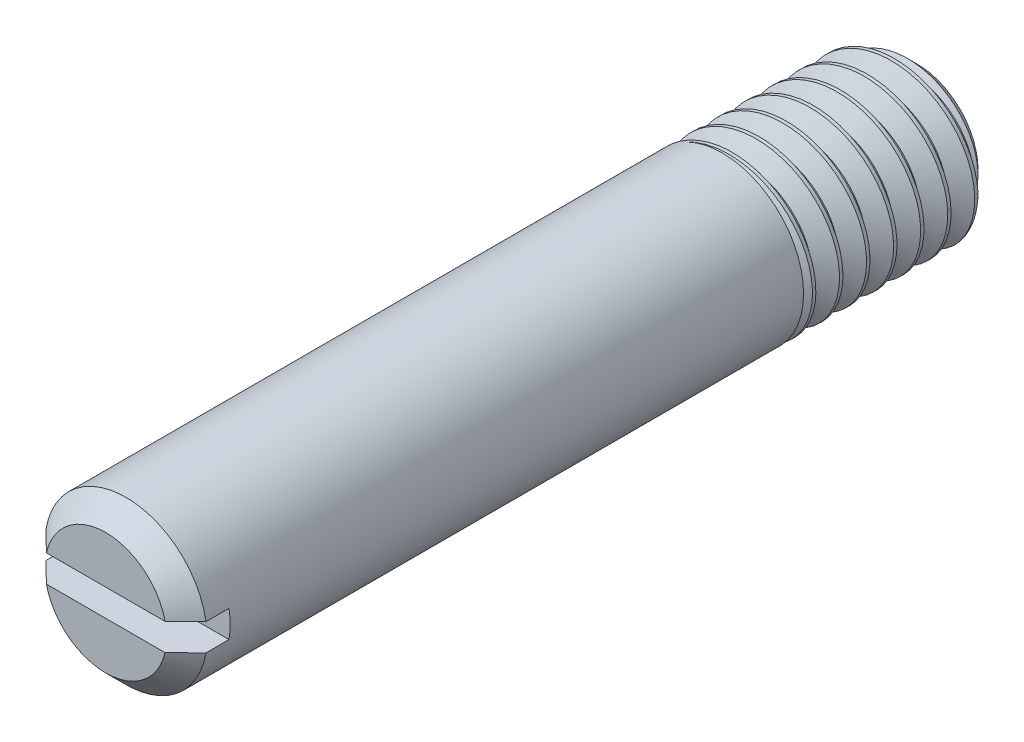
SolidWorks part; units mm, degrees
ref_plane "Front Plane" through (0, 0, 0) normal (0, 0, 1) x (1, 0, 0)
ref_plane "Top Plane" through (0, 0, 0) normal (0, 1, 0) x (1, 0, 0)
ref_plane "Right Plane" through (0, 0, 0) normal (1, 0, 0) x (0, 0, -1)
sketch "Sketch1" plane through (0, 0, 0) normal (1, 0, 0) x (0, 0, -1)
  line L0 (-22.8, 0) -> (7.2, 0) construction
  line L1 (7.2, 3) -> (7.2, -3) construction
  line L2 (-22.8, 0.5) -> (-22.8, -0.5) construction
  line L3 (-22.8, -0.5) -> (-21.2, -0.5) construction
  line L4 (7.2, 3) -> (6.2, 3) construction
  line L5 (6.2, 3) -> (0, 3) construction
  line L6 (0, 3) -> (-22.8, 3) construction
  point P5 (7.2, 0)
  point P9 (0, 0)
  dimension "Oall Length" = 30
  dimension "Thread Diameter" = 6
  dimension "Thread Length" = 7.2
  dimension "Slot Width n" = 1
  dimension "Slot Depth t" = 1.6
  dimension "Pitch" = 1
sketch "Sketch2" plane through (0, 0, 0) normal (1, 0, 0) x (0, 0, -1)
  line L0 (7.2, 0) -> (7.2, 3)
  line L1 (7.2, 3) -> (-22.8, 3)
  line L2 (-22.8, 3) -> (-22.8, 0)
  line L3 (-22.8, 0) -> (7.2, 0)
revolve "Revolve1" add sketch "Sketch2" angle 360 about L0
fillet "Chamfer2" radius 0.75 2 edges at (3, 0, 22.8) (3, 0, -7.2) profile chamfer
sketch "Sketch3" plane through (0, 0, 0) normal (1, 0, 0) x (0, 0, -1)
  line L0 (-21.2, -0.5) -> (-22.8, -0.5)
  line L1 (-22.8, -0.5) -> (-22.8, 0.5)
  line L2 (-22.8, 0.5) -> (-21.2, 0.5)
  line L3 (-21.2, 0.5) -> (-21.2, -0.5)
extrude "Cut-Extrude1" cut sketch "Sketch3" against normal through all both and the other way through all
sketch "Sketch4" plane through (0, 0, -7.2) normal (0, 0, -1) x (-1, 0, 0)
  circle A0 centre (0, 0) radius 3
curve "Helix/Spiral1" pitch 1 height 8.2 radius 3 centre (0, 0, -7.2) axis (0, 0, 1) start towards (0, 1, 0) parameters "pitch"=1
sketch "Sketch5" plane through (0, 0, 0) normal (1, 0, 0) x (0, 0, -1)
  line L0 (7.2, 3) -> (8.075, 3) construction
  line L1 (8.075, 3) -> (7.6375, 2.2422) construction
  line L2 (7.6375, 2.2422) -> (7.2, 3) construction
  line L3 (7.575, 2.3505) -> (7.7, 2.3505) construction
  line L4 (7.6375, 2.3505) -> (7.6375, 3) construction
  line L5 (7.3875, 2.6752) -> (7.8875, 2.6752) construction
  line L6 (7.2, 3) -> (8.075, 3)
  line L7 (8.075, 3) -> (7.7, 2.3505)
  line L8 (7.7, 2.3505) -> (7.575, 2.3505)
  line L9 (7.575, 2.3505) -> (7.2, 3)
  point P7 (7.6375, 2.6752)
  dimension "D1" = 0.125
  dimension "D2" = 0.5
sweep "Cut-Sweep1" cut profiles "Sketch5" path "Helix/Spiral1" align with end faces yes
sketch "Sketch6" plane through (0, 0, 0) normal (0, 0, 1) x (1, 0, 0)
  circle A1 centre (0, 0) radius 3
  circle A2 centre (0, 0) radius 3
  dimension "D1" = 0
extrude "Boss-Extrude2" add sketch "Sketch6" along normal blind 1
ref_axis "Center Axis 1" through (0, 0, -6.45) along (0, 0, 1)
ref_plane "Contact Plane 1" through (0, 0, 0) normal (0, 0, 1) x (1, 0, 0)
move or copy body "Body-Move/Copy1" [suppressed] bodies to move or copy 315
equation "\"3..6250in\"=4.625"
equation "\"Slot Width n@Sketch1\"=\"Pitch@Sketch1\""
equation "\"Slot Depth t@Sketch1\"=\"Pitch@Sketch1\"*1.6"
equation "\"D1@Chamfer2\"=\"Pitch@Sketch1\"*.75"
equation "\"D1@Sketch5\"=\"Pitch@Sketch1\"*.125"
equation "\"D2@Sketch5\"=\"Pitch@Sketch1\"*.5"
equation "\"D3@Helix/Spiral1\"=\"Thread Length@Sketch1\"+(\"Pitch@Sketch1\")"
equation "\"D1@Boss-Extrude2\"=\"Pitch@Sketch1\""
